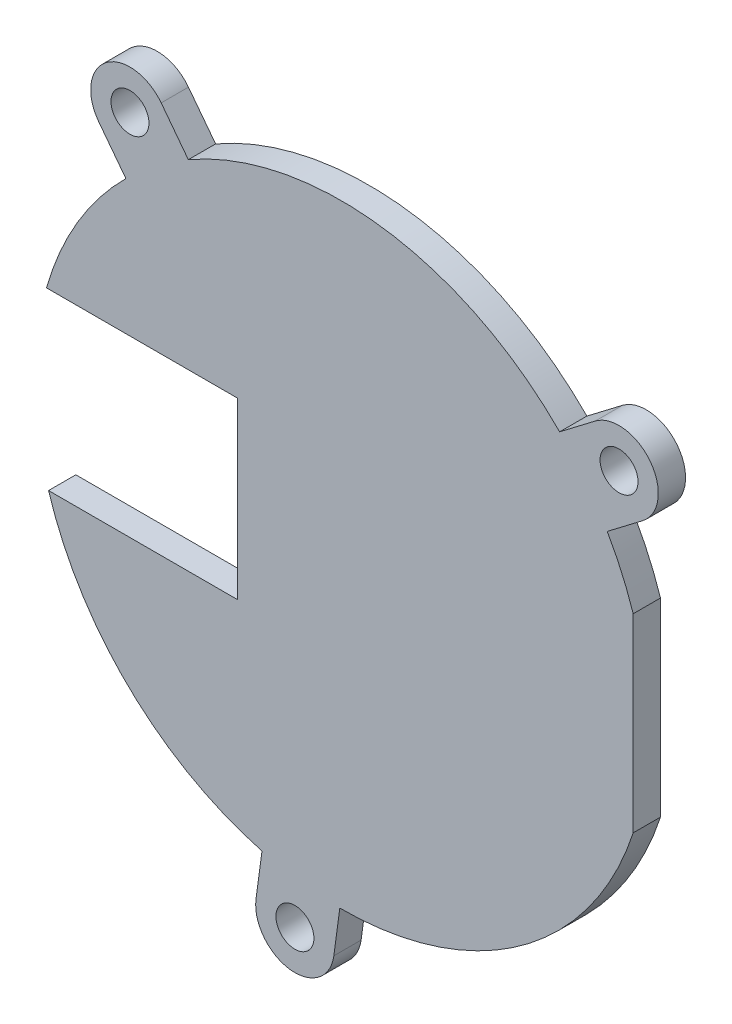
SolidWorks part; units mm, degrees
ref_plane "Front Plane" through (0, 0, 0) normal (0, 0, 1) x (1, 0, 0)
ref_plane "Top Plane" through (0, 0, 0) normal (0, 1, 0) x (1, 0, 0)
ref_plane "Right Plane" through (0, 0, 0) normal (1, 0, 0) x (0, 0, -1)
sketch "Sketch1" plane through (0, 0, 0) normal (0, 0, 1) x (1, 0, 0)
  line L0 (-6.0563, 4.8768) -> (-17.1812, 4.8768) construction
  line L2 (-17.0607, -5.2832) -> (-6.0563, -5.2832) construction
  line L3 (-4.9801, -19.8325) -> (-4.6318, -17.2489) construction
  line L4 (-0.1008, -17.8597) -> (-0.449, -20.4433) construction
  line L5 (16.9841, -5.5245) -> (16.9841, 5.5245) construction
  line L6 (17.5451, 10.5023) -> (15.472, 8.9216) construction
  line L7 (14.7731, 14.138) -> (12.7, 12.5574) construction
  line L8 (-8.9216, 15.472) -> (-10.5023, 17.5451) construction
  line L9 (-14.138, 14.7731) -> (-12.5574, 12.7) construction
  line L10 (-6.0563, 4.8768) -> (-17.1812, 4.8768)
  line L11 (-6.0563, 4.8768) -> (-6.0563, -5.2832)
  line L12 (-17.0607, -5.2832) -> (-6.0563, -5.2832)
  line L13 (-4.9801, -19.8325) -> (-4.6318, -17.2489)
  line L14 (-0.1008, -17.8597) -> (-0.449, -20.4433)
  line L15 (16.9841, -5.5245) -> (16.9841, 5.5245)
  line L16 (17.5451, 10.5023) -> (15.472, 8.9216)
  line L17 (14.7731, 14.138) -> (12.7, 12.5574)
  line L18 (-8.9216, 15.472) -> (-10.5023, 17.5451)
  line L19 (-14.138, 14.7731) -> (-12.5574, 12.7)
  arc A0 (-17.0607, -5.2832) -> (-4.6318, -17.2489) centre (0, 0) ccw construction
  arc A1 (-4.9801, -19.8325) -> (-0.449, -20.4433) centre (-2.7145, -20.1379) ccw construction
  circle A2 centre (-2.7145, -20.1379) radius 1.1049 construction
  arc A3 (-0.1008, -17.8597) -> (16.9841, -5.5245) centre (0, 0) ccw construction
  arc A4 (16.9841, 5.5245) -> (15.472, 8.9216) centre (0, 0) ccw construction
  arc A5 (17.5451, 10.5023) -> (14.7731, 14.138) centre (16.1591, 12.3201) ccw construction
  arc A6 (12.7, 12.5574) -> (-8.9216, 15.472) centre (0, 0) ccw construction
  arc A7 (-10.5023, 17.5451) -> (-14.138, 14.7731) centre (-12.3201, 16.1591) ccw construction
  arc A8 (-12.5574, 12.7) -> (-17.1812, 4.8768) centre (0, 0) ccw construction
  arc A9 (-17.0607, -5.2832) -> (-4.6318, -17.2489) centre (0, 0) ccw
  arc A10 (-4.9801, -19.8325) -> (-0.449, -20.4433) centre (-2.7145, -20.1379) ccw
  circle A11 centre (-2.7145, -20.1379) radius 1.1049
  arc A12 (-0.1008, -17.8597) -> (16.9841, -5.5245) centre (0, 0) ccw
  arc A13 (16.9841, 5.5245) -> (15.472, 8.9216) centre (0, 0) ccw
  arc A14 (17.5451, 10.5023) -> (14.7731, 14.138) centre (16.1591, 12.3201) ccw
  arc A15 (12.7, 12.5574) -> (-8.9216, 15.472) centre (0, 0) ccw
  arc A16 (-10.5023, 17.5451) -> (-14.138, 14.7731) centre (-12.3201, 16.1591) ccw
  arc A17 (-12.5574, 12.7) -> (-17.1812, 4.8768) centre (0, 0) ccw
  circle A18 centre (-12.3201, 16.1591) radius 1.1049 construction
  circle A19 centre (16.1591, 12.3201) radius 1.1049 construction
  circle A20 centre (-12.3201, 16.1591) radius 1.1049
  circle A21 centre (16.1591, 12.3201) radius 1.1049
extrude "Boss-Extrude1" add sketch "Sketch1" along normal blind 1.5875
